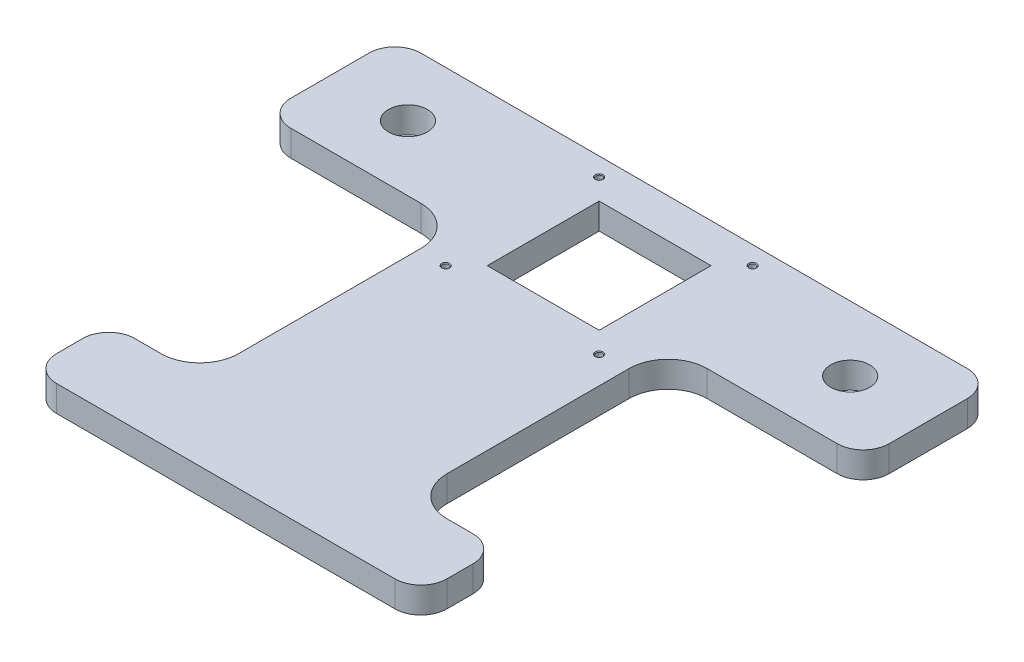
SolidWorks part; units mm, degrees
ref_plane "Vorne" through (0, 0, 0) normal (0, 0, 1) x (1, 0, 0)
ref_plane "Oben" through (0, 0, 0) normal (0, 1, 0) x (1, 0, 0)
ref_plane "Rechts" through (0, 0, 0) normal (1, 0, 0) x (0, 0, -1)
ref_plane "E_Boden" through (0, 1, 0) normal (0, 1, 0) x (1, 0, 0)
sketch "Skizze1" plane through (0, 0, 0) normal (0, 1, 0) x (1, 0, 0)
  line L0 (0, -84.2382) -> (0, 127.1868) construction
  line L1 (-165.4867, 0) -> (188.3198, 0) construction
  line L2 (-105, 90) -> (105, 90)
  line L3 (-115, 80) -> (-115, 50)
  line L8 (-105, 40) -> (-55, 40)
  line L9 (-40, 25) -> (-40, -45)
  line L10 (-55, -60) -> (-65, -60)
  line L11 (-75, -70) -> (-75, -80)
  line L12 (-65, -90) -> (65, -90)
  line L13 (75, -70) -> (75, -80)
  line L14 (55, -60) -> (65, -60)
  line L15 (40, 25) -> (40, -45)
  line L16 (105, 40) -> (55, 40)
  line L17 (115, 80) -> (115, 50)
  arc A0 (40, 25) -> (55, 40) centre (55, 25) cw
  arc A1 (55, -60) -> (40, -45) centre (55, -45) cw
  arc A2 (-40, -45) -> (-55, -60) centre (-55, -45) cw
  arc A3 (-55, 40) -> (-40, 25) centre (-55, 25) cw
  arc A4 (75, -70) -> (65, -60) centre (65, -70) ccw
  arc A5 (75, -80) -> (65, -90) centre (65, -80) cw
  arc A6 (-75, -80) -> (-65, -90) centre (-65, -80) ccw
  arc A7 (-65, -60) -> (-75, -70) centre (-65, -70) ccw
  arc A8 (-115, 50) -> (-105, 40) centre (-105, 50) ccw
  arc A9 (105, 40) -> (115, 50) centre (105, 50) ccw
  arc A10 (115, 80) -> (105, 90) centre (105, 80) ccw
  arc A11 (-105, 90) -> (-115, 80) centre (-105, 80) ccw
  point P15 (0, -90)
  point P16 (0, 90)
  point P22 (40, 40)
  point P25 (40, -60)
  point P28 (-40, -60)
  point P31 (-40, 40)
  point P34 (75, -60)
  point P37 (75, -90)
  point P40 (-75, -90)
  point P43 (-75, -60)
  point P46 (-115, 40)
  point P49 (115, 40)
  point P52 (115, 90)
  point P55 (-115, 90)
  dimension "D7" = 15
  dimension "D8" = 10
  dimension "D1" = 230
  dimension "D2" = 50
  dimension "D3" = 130
  dimension "D4" = 150
  dimension "D5" = 80
  dimension "D6" = 30
extrude "Aufsatz-Linear austragen1" add sketch "Skizze1" along normal blind 10
hole_wizard "Ø15.0 (15) Durchmesser Bohrung1" positions "Skizze6" profile "Skizze7" hole size "Ø15.0" standard "DIN" end condition through all
sketch "Skizze6" plane through (0, 10, 0) normal (0, 1, 0) x (1, 0, 0)
  line L2 (105, 90) -> (-105, 90) construction
  line L3 (0, 90) -> (0, -90) construction
  line L4 (-65, -90) -> (65, -90) construction
  point P0 (-85, 65)
  point P2 (85, 65)
  dimension "D1" = 25
  dimension "D2" = 25
  dimension "D3" = 170
sketch "Skizze7" plane through (-85, 10, -65) normal (1, 0, 0) x (0, 0, 1)
  line L0 (0, 0) -> (0, 10)
  line L1 (0, 10) -> (7.5, 10)
  line L2 (7.5, 10) -> (7.5, 0)
  line L5 (7.5, 0) -> (0, 0)
  line L11 (0, -6.35) -> (0, 107.95) construction
  dimension "Bohrerdurchmesser" = 15
  dimension "Bohrungstiefe" = 10
sketch "Skizze8" plane through (0, 10, 0) normal (0, 1, 0) x (1, 0, 0)
  line L0 (0, 90) -> (0, -90) construction
  line L3 (105, 90) -> (-105, 90) construction
  line L4 (-21.5, 75) -> (21.5, 75)
  line L5 (-21.5, 75) -> (-21.5, 32)
  line L6 (-21.5, 32) -> (21.5, 32)
  line L7 (21.5, 75) -> (21.5, 32)
  line L8 (-65, -90) -> (65, -90) construction
  dimension "D1" = 43
  dimension "D2" = 43
  dimension "D3" = 15
extrude "Schnitt-Linear austragen2" cut sketch "Skizze8" against normal blind 10
hole_wizard "M3 Gewindebohrung1" positions "Skizze9" profile "Skizze10" tap size "M3" standard "DIN"
sketch "Skizze9" plane through (0, 10, 0) normal (0, 1, 0) x (1, 0, 0)
  line L0 (0, 75) -> (0, 32) construction
  line L1 (21.5, 75) -> (-21.5, 75) construction
  line L2 (-21.5, 32) -> (21.5, 32) construction
  line L4 (-21.5, 53.5) -> (21.5, 53.5) construction
  line L5 (-21.5, 75) -> (-21.5, 32) construction
  line L6 (21.5, 32) -> (21.5, 75) construction
  point P0 (-29.5, 83)
  point P2 (-29.5, 24)
  point P4 (29.5, 24)
  point P6 (29.5, 83)
  point P32 (29.5, 83)
  dimension "D1" = 8
  dimension "D2" = 8
sketch "Skizze10" plane through (-29.5, 10, -83) normal (1, 0, 0) x (0, 0, 1)
  line L0 (0, 0) -> (0, 8.7511)
  line L1 (0, 8.7511) -> (1.25, 8)
  line L2 (1.25, 8) -> (1.25, 0.275)
  line L3 (1.25, 0.275) -> (1.525, 0)
  line L5 (1.525, 0) -> (0, 0)
  line L6 (-1.25, 0.275) -> (-1.525, 0) construction
  line L10 (0, 8.7511) -> (-1.25, 8) construction
  line L11 (0, -6.35) -> (0, 107.95) construction
  dimension "Bohrerdurchmesser" = 2.5
  dimension "Bohrungstiefe" = 8
  dimension "Senkdurchmesser (Oben)" = 3.05
  dimension "Senkwinkel (Oben)" = 90
  dimension "Spitzenwinkel" = 118
cosmetic thread "Bohrungsgewinde1" parameters "D1"=6, "D2"=3
cosmetic thread "Bohrungsgewinde2" parameters "D1"=6, "D2"=3
cosmetic thread "Bohrungsgewinde3" parameters "D1"=6, "D2"=3
cosmetic thread "Bohrungsgewinde4" parameters "D1"=6, "D2"=3
